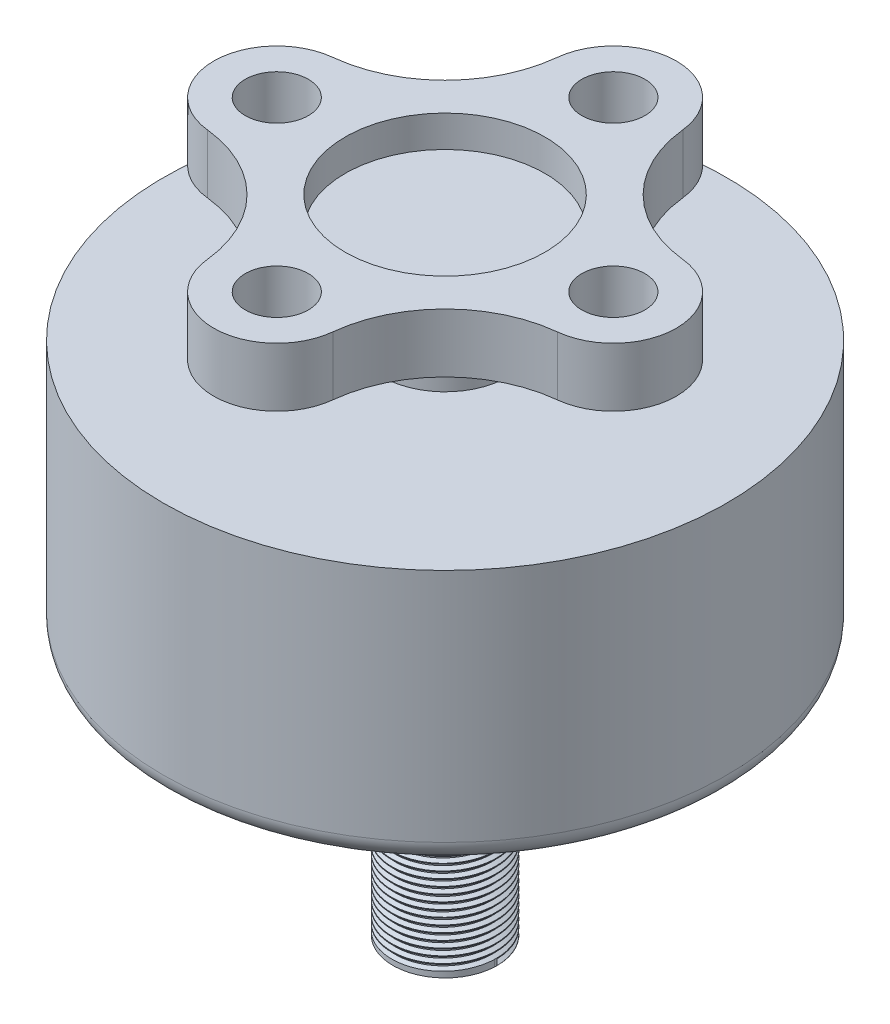
SolidWorks part; units mm, degrees
ref_plane "前视基准面" through (0, 0, 0) normal (0, 0, 1) x (1, 0, 0)
ref_plane "上视基准面" through (0, 0, 0) normal (0, 1, 0) x (1, 0, 0)
ref_plane "右视基准面" through (0, 0, 0) normal (1, 0, 0) x (0, 0, -1)
sketch "草图1" plane through (0, 0, 0) normal (0, 1, 0) x (1, 0, 0)
  circle A0 centre (0, 0) radius 13.4
  point P3 (0, 0)
  dimension "D1" = 26.8
extrude "凸台-拉伸1" add sketch "草图1" along normal blind 12.2
sketch "草图2" plane through (0, 0, 0) normal (0, -1, 0) x (1, 0, 0)
  circle A0 centre (0, 0) radius 2.48
  dimension "D1" = 4.96
extrude "凸台-拉伸2" add sketch "草图2" along normal blind 12.3
thread "螺纹线1" pitch 0.3175 method cut profile "螺纹线轮廓1" start angle 0, offset 0, length 7.3, pitch 0.3175, diameter 4.96
ref_plane "基准面4" through (2.48, -12.3, 0) normal (0, 0, 1) x (1, 0, 0)
sketch "螺纹线轮廓1" plane through (2.48, -12.3, 0) normal (0, 0, 1) x (1, 0, 0)
  line L0 (0, 0) -> (0, 0.3175) construction
  line L11 (0, 0) -> (0, 0.2778)
  line L12 (0, 0.2778) -> (-0.1719, 0.1786)
  line L13 (-0.1719, 0.1786) -> (-0.1719, 0.0992)
  line L15 (-0.1719, 0.0992) -> (0, 0)
  line L17 (-0.1719, 0.1389) -> (0, 0.1389) construction
  point P2 (0, 0)
  dimension "Pitch" = 0.3175
  dimension "Profile_Angle" = 60
  dimension "Profile_Land" = 0.0794
  dimension "Profile_Height" = 0.1719
sketch "草图5" plane through (0, 0, 0) normal (0, -1, 0) x (1, 0, 0)
  line L0 (0, 13.8846) -> (0, -14.6775) construction
  line L1 (-15.1515, 0) -> (15.6687, 0) construction
  line L2 (-11.4594, 11.4594) -> (11.8728, -11.8728) construction
  line L3 (11.4594, 11.4594) -> (-11.8728, -11.8728) construction
  line L4 (-6.364, 7.7782) -> (-2.1213, 3.5355)
  line L5 (-1, 10) -> (-1, 4)
  line L6 (0, 0) -> (-5.7471, 13.8748) construction
  line L7 (1, 10) -> (1, 4)
  line L8 (6.364, 7.7782) -> (2.1213, 3.5355)
  line L9 (7.7782, 6.364) -> (3.5355, 2.1213)
  line L10 (10, 1) -> (4, 1)
  line L11 (10, -1) -> (4, -1)
  line L12 (7.7782, -6.364) -> (3.5355, -2.1213)
  line L13 (6.364, -7.7782) -> (2.1213, -3.5355)
  line L14 (1, -10) -> (1, -4)
  line L15 (-1, -10) -> (-1, -4)
  line L16 (-6.364, -7.7782) -> (-2.1213, -3.5355)
  line L17 (-7.7782, -6.364) -> (-3.5355, -2.1213)
  line L18 (-10, -1) -> (-4, -1)
  line L19 (-10, 1) -> (-4, 1)
  line L20 (-7.7782, 6.364) -> (-3.5355, 2.1213)
  arc A0 (-6.364, 7.7782) -> (-1, 10) centre (-1.6725, 4.0378) cw
  arc A1 (-2.1213, 3.5355) -> (-1, 4) centre (-0.4363, 1.0534) cw
  arc A2 (1, 10) -> (6.364, 7.7782) centre (1.6725, 4.0378) cw
  arc A3 (1, 4) -> (2.1213, 3.5355) centre (0.4363, 1.0534) cw
  arc A4 (7.7782, 6.364) -> (10, 1) centre (4.0378, 1.6725) cw
  arc A5 (3.5355, 2.1213) -> (4, 1) centre (1.0534, 0.4363) cw
  arc A6 (10, -1) -> (7.7782, -6.364) centre (4.0378, -1.6725) cw
  arc A7 (4, -1) -> (3.5355, -2.1213) centre (1.0534, -0.4363) cw
  arc A8 (6.364, -7.7782) -> (1, -10) centre (1.6725, -4.0378) cw
  arc A9 (2.1213, -3.5355) -> (1, -4) centre (0.4363, -1.0534) cw
  arc A10 (-1, -10) -> (-6.364, -7.7782) centre (-1.6725, -4.0378) cw
  arc A11 (-1, -4) -> (-2.1213, -3.5355) centre (-0.4363, -1.0534) cw
  arc A12 (-7.7782, -6.364) -> (-10, -1) centre (-4.0378, -1.6725) cw
  arc A13 (-3.5355, -2.1213) -> (-4, -1) centre (-1.0534, -0.4363) cw
  arc A14 (-10, 1) -> (-7.7782, 6.364) centre (-4.0378, 1.6725) cw
  arc A15 (-4, 1) -> (-3.5355, 2.1213) centre (-1.0534, 0.4363) cw
  point P61 (0, 0)
  dimension "D5" = 6
  dimension "D6" = 3
  dimension "D7" = 4
  dimension "D9" = 8
  dimension "D1" = 45
  dimension "D2" = 1
  dimension "D3" = 1
  dimension "D4" = 22.5
  dimension "D8" = 10
extrude "切除-拉伸1" cut sketch "草图5" against normal blind 3
sketch "草图6" plane through (0, 12.2, 0) normal (0, 1, 0) x (1, 0, 0)
  circle A0 centre (0, 0) radius 3
  dimension "D1" = 6
extrude "凸台-拉伸3" add sketch "草图6" along normal blind 3.2
sketch "草图7" plane through (0, 15.4, 0) normal (0, 1, 0) x (1, 0, 0)
  line L0 (0, 0) -> (0, 14.057) construction
  line L1 (0, 0) -> (17.9785, 0) construction
  circle A0 centre (-8, 0) radius 1.5
  circle A1 centre (8, 0) radius 1.5
  circle A2 centre (0, 8) radius 1.5
  circle A3 centre (0, -8) radius 1.5
  circle A4 centre (0, 0) radius 3 construction
  circle A5 centre (0, 0) radius 3 construction
  arc A6 (2.9832, 8.3166) -> (-2.9832, 8.3166) centre (0, 8) ccw
  arc A7 (8.3166, -2.9832) -> (8.3166, 2.9832) centre (8, 0) ccw
  arc A8 (-2.9832, -8.3166) -> (2.9832, -8.3166) centre (0, -8) ccw
  arc A9 (-8.3166, 2.9832) -> (-8.3166, -2.9832) centre (-8, 0) ccw
  arc A10 (-8.3166, 2.9832) -> (-2.9832, 8.3166) centre (-8.9497, 8.9497) ccw
  arc A11 (8.3166, 2.9832) -> (2.9832, 8.3166) centre (8.9497, 8.9497) cw
  arc A12 (8.3166, -2.9832) -> (2.9832, -8.3166) centre (8.9497, -8.9497) ccw
  arc A13 (-8.3166, -2.9832) -> (-2.9832, -8.3166) centre (-8.9497, -8.9497) cw
  point P20 (0, 0)
  point P24 (0, 0)
  dimension "D1" = 3
  dimension "D4" = 8
  dimension "D5" = 8
  dimension "D6" = 6
  dimension "D7" = 6
  dimension "D2" = 16
  dimension "D3" = 16
extrude "凸台-拉伸4" add sketch "草图7" along normal blind 2.8
sketch "草图8" plane through (0, 18.2, 0) normal (0, 1, 0) x (1, 0, 0)
  circle A0 centre (0, 0) radius 4.75
  dimension "D1" = 9.5
extrude "切除-拉伸2" cut sketch "草图8" against normal blind 1.5
fillet "圆角1" radius 1 1 edges at (0, 0, 13.4)
